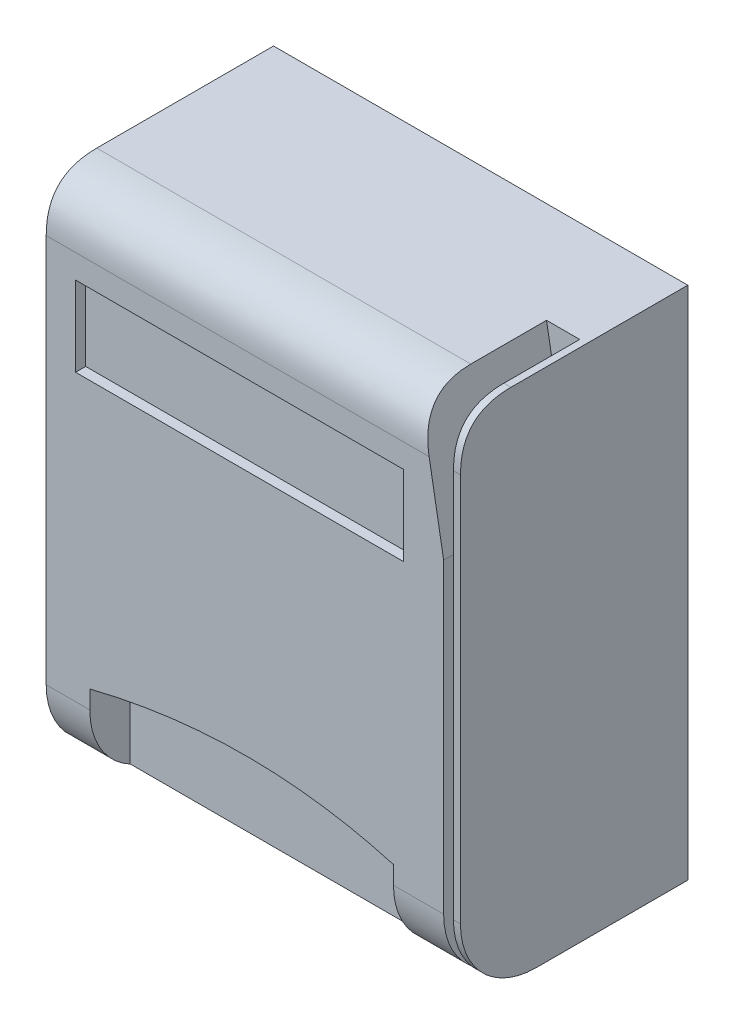
SolidWorks part; units mm, degrees
ref_plane "Front Plane" through (0, 0, 0) normal (0, 0, 1) x (1, 0, 0)
ref_plane "Top Plane" through (0, 0, 0) normal (0, 1, 0) x (1, 0, 0)
ref_plane "Right Plane" through (0, 0, 0) normal (1, 0, 0) x (0, 0, -1)
sketch "Sketch1" plane through (0, 0, 0) normal (0, 0, 1) x (1, 0, 0)
  line L1 (-45.7163, 62.8004) -> (36.2837, 62.8004)
  line L2 (-45.7163, 62.8004) -> (-45.7163, -39.1996)
  line L3 (-45.7163, -39.1996) -> (36.2837, -39.1996)
  line L4 (36.2837, 62.8004) -> (36.2837, -39.1996)
  dimension "D1" = 82
  dimension "D2" = 102
extrude "Boss-Extrude1" add sketch "Sketch1" along normal blind 45
fillet "Fillet1" radius 15 1 edges at (-4.7163, -39.1996, 45)
fillet "Fillet2" radius 10 1 edges at (-4.7163, 62.8004, 45)
sketch "Sketch2" plane through (0, 0, 45) normal (0, 0, 1) x (1, 0, 0)
  line L1 (34.8879, 65.0411) -> (32.9524, 65.0411)
  line L2 (34.8879, 65.0411) -> (34.8879, -42.9984)
  line L3 (34.8879, -42.9984) -> (32.9524, -42.9984)
  line L4 (32.9524, 65.0411) -> (32.9524, -42.9984)
extrude "Cut-Extrude1" cut sketch "Sketch2" against normal blind 25
sketch "Sketch3" plane through (0, 0, 45) normal (0, 0, 1) x (1, 0, 0)
  line L0 (32.9524, 36.5117) -> (28.2041, 63.476)
  line L1 (32.9524, 52.8004) -> (32.9524, -24.1996) construction
  line L2 (28.2041, 63.476) -> (32.9524, 63.476)
  line L3 (32.9524, 63.476) -> (32.9524, 36.5117)
extrude "Cut-Extrude2" cut sketch "Sketch3" against normal blind 25
sketch "Sketch4" plane through (0, 0, 45) normal (0, 0, 1) x (1, 0, 0)
  line L1 (-39.9018, 48.0878) -> (25.0426, 48.0878)
  line L2 (-39.9018, 48.0878) -> (-39.9018, 32.2785)
  line L3 (-39.9018, 32.2785) -> (25.0426, 32.2785)
  line L4 (25.0426, 48.0878) -> (25.0426, 32.2785)
extrude "Cut-Extrude3" cut sketch "Sketch4" against normal blind 2
sketch "Sketch5" plane through (0, 0, 45) normal (0, 0, 1) x (1, 0, 0)
  line L0 (-37.0796, -20.5979) -> (22.8157, -20.5979)
  spline S0 degree 2 poles (-37.0796, -20.5979) (-5.102, -12.5909) (22.8157, -20.5979) knots 0 0 0 0.561199 0.561199 0.561199
  point P4 (22.8157, -20.5979)
extrude "Cut-Extrude4" cut sketch "Sketch5" against normal blind 8
sketch "Sketch6" plane through (0, 0, 45) normal (0, 0, 1) x (1, 0, 0)
  line L1 (-37.0796, -20.5979) -> (23.0256, -20.5979)
  line L2 (-37.0796, -20.5979) -> (-37.0796, -45.583)
  line L3 (-37.0796, -45.583) -> (23.0256, -45.583)
  line L4 (23.0256, -20.5979) -> (23.0256, -45.583)
extrude "Cut-Extrude5" cut sketch "Sketch6" against normal blind 8
sketch "Sketch7" plane through (0, 0, 0) normal (0, 0, -1) x (-1, 0, 0)
  line L0 (-36.2837, 62.8004) -> (45.7163, 62.8004) construction
  line L1 (-36.2837, -39.1996) -> (-36.2837, 62.8004) construction
  line L2 (45.7163, -39.1996) -> (-36.2837, -39.1996) construction
  circle A0 centre (-28.7837, 47.8004) radius 1.5
  circle A1 centre (38.2163, 47.8004) radius 1.5
  circle A2 centre (38.2163, -24.1996) radius 1.5
  circle A3 centre (-28.7837, -24.1996) radius 1.5
  point P0 (4.7163, 62.8004)
  point P1 (-36.2837, 11.8004)
  dimension "D1" = 3
  dimension "D2" = 33.5
  dimension "D3" = 33.5
  dimension "D4" = 15
  dimension "D5" = 15
extrude "Cut-Extrude6" cut sketch "Sketch7" against normal blind 8
